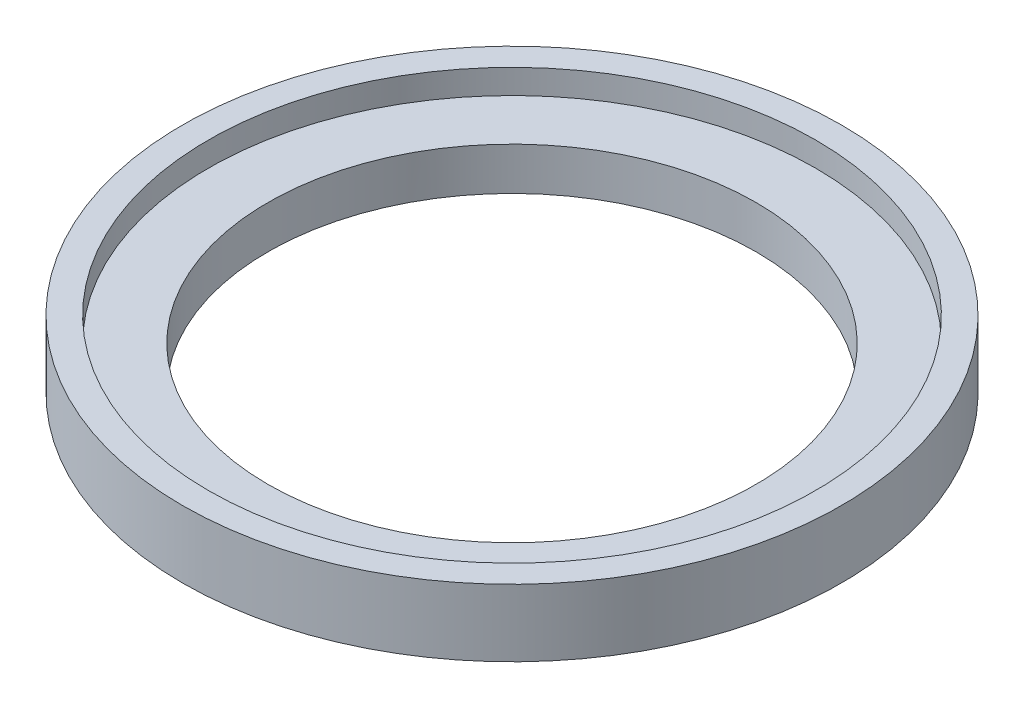
SolidWorks part; units mm, degrees
ref_plane "Front Plane" through (0, 0, 0) normal (0, 0, 1) x (1, 0, 0)
ref_plane "Top Plane" through (0, 0, 0) normal (0, 1, 0) x (1, 0, 0)
ref_plane "Right Plane" through (0, 0, 0) normal (1, 0, 0) x (0, 0, -1)
sketch "Sketch1" plane through (0, 0, 0) normal (0, 1, 0) x (1, 0, 0)
  circle A0 centre (0, 0) radius 54
  circle A1 centre (0, 0) radius 40
  dimension "D1" = 108
  dimension "D2" = 80
extrude "Boss-Extrude1" add sketch "Sketch1" along normal blind 2.5
sketch "Sketch2" plane through (0, 2.5, 0) normal (0, 1, 0) x (1, 0, 0)
  circle A0 centre (0, 0) radius 54
  circle A1 centre (0, 0) radius 49.75
  circle A2 centre (0, 0) radius 54 construction
  dimension "D1" = 4.25
extrude "Boss-Extrude2" add sketch "Sketch2" along normal blind 4
sketch "Sketch3" plane through (0, 0, 0) normal (0, -1, 0) x (1, 0, 0)
  circle A0 centre (0, 0) radius 54
  circle A1 centre (0, 0) radius 49.5
  circle A2 centre (0, 0) radius 54 construction
  circle A3 centre (0, 0) radius 40
  circle A4 centre (0, 0) radius 44.5
  circle A5 centre (0, 0) radius 40 construction
  circle M4 centre (0, 0) radius 54
  circle M5 centre (0, 0) radius 40
  dimension "D1" = 4.5
  dimension "D2" = 4.5
extrude "Boss-Extrude3" add sketch "Sketch3" along normal blind 4.5 contours A4 M5 | A1 M4 region at (-52.4726, 0, 0) region at (-43.2413, 0, 0)
